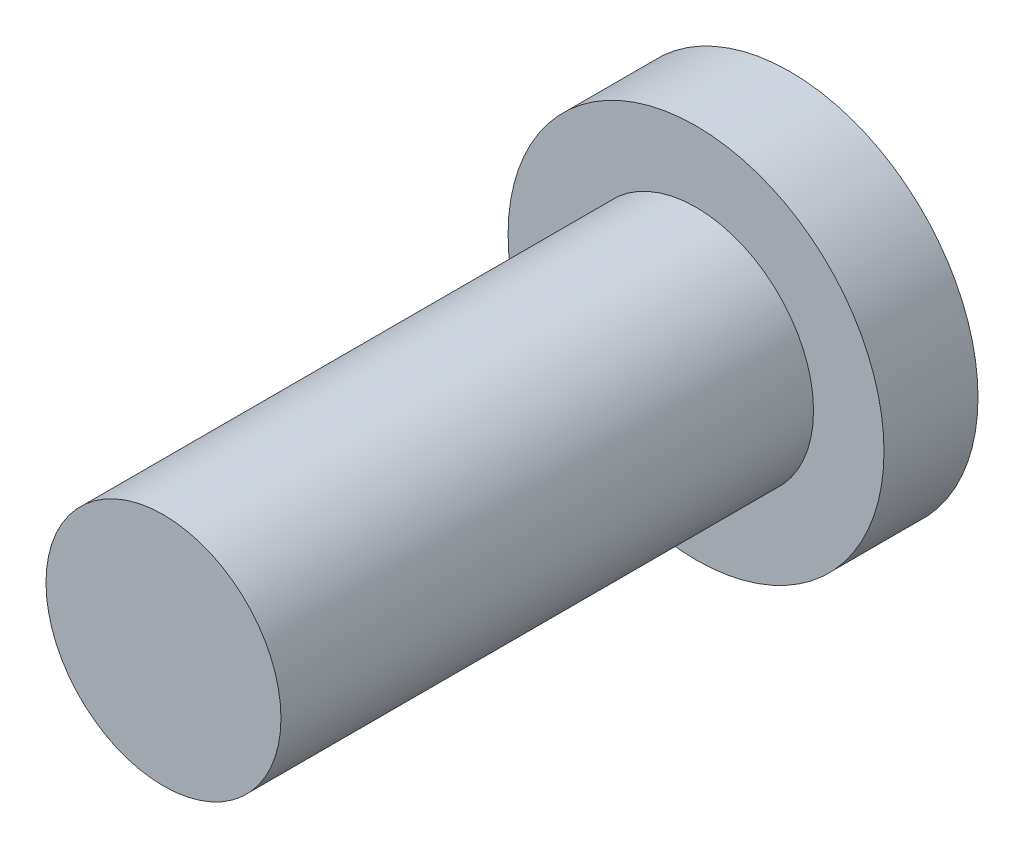
SolidWorks part; units mm, degrees
ref_plane "Front Plane" through (0, 0, 0) normal (0, 0, 1) x (1, 0, 0)
ref_plane "Top Plane" through (0, 0, 0) normal (0, 1, 0) x (1, 0, 0)
ref_plane "Right Plane" through (0, 0, 0) normal (1, 0, 0) x (0, 0, -1)
sketch "Sketch1" plane through (0, 0, 0) normal (0, 0, 1) x (1, 0, 0)
  circle A0 centre (0, 0) radius 3.75
  circle A1 centre (0, 0) radius 6
  dimension "D1" = 7.5
  dimension "D2" = 12
extrude "Boss-Extrude1" add sketch "Sketch1" along normal blind 3
extrude "Boss-Extrude2" add sketch "Sketch1<2>" along normal blind 20 contours A0 region at (0, 0, 0)
sketch "Sketch1<2>" plane through (0, 0, 0) normal (0, 0, 1) x (1, 0, 0) same geometry as "Sketch1"
